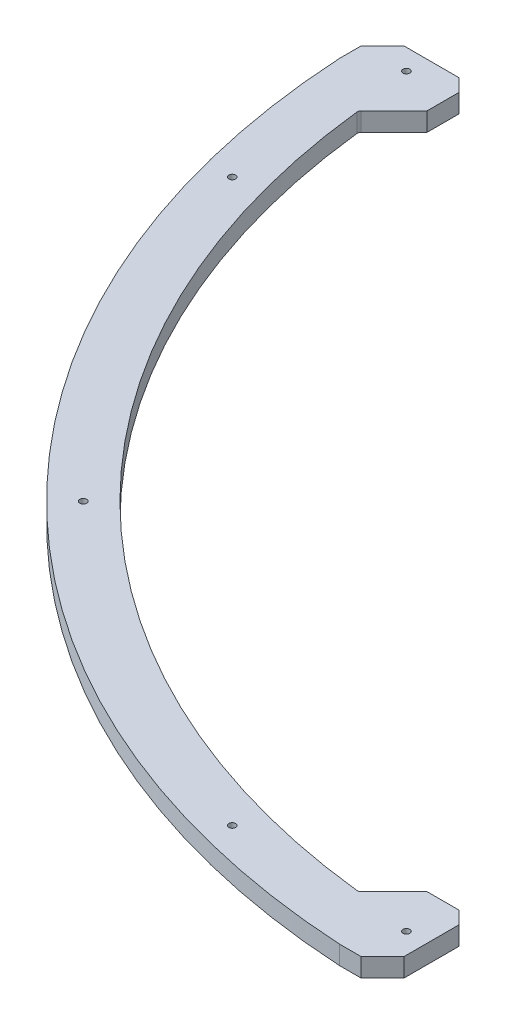
SolidWorks part; units mm, degrees
material "Pine"
ref_plane "Front Plane" through (0, 0, 0) normal (0, 0, 1) x (1, 0, 0)
ref_plane "Top Plane" through (0, 0, 0) normal (0, 1, 0) x (1, 0, 0)
ref_plane "Right Plane" through (0, 0, 0) normal (1, 0, 0) x (0, 0, -1)
ref_plane "Plane1" through (0, 0, 0) normal (0.7071, 0, -0.7071) x (-0.7071, 0, -0.7071)
ref_axis "Axis1" through (0, -0.9128, 0) along (0, 1, 0)
sketch "Sketch1" plane through (0, 0, 0) normal (0, 1, 0) x (1, 0, 0)
  circle A0 centre (0, 0) radius 796.925
  circle A1 centre (0, 0) radius 746.125
  dimension "D1" = 1593.85
  dimension "D2" = 50.8
extrude "Boss-Extrude1" add sketch "Sketch1" along normal blind 18.2562
sketch "Sketch3" plane through (0, 18.2562, 0) normal (0, 1, 0) x (1, 0, 0)
  line L0 (-796.925, 0) -> (0, 0)
  line L1 (0, 0) -> (0, -796.925)
  circle A0 centre (0, 0) radius 796.925 construction
  arc A1 (0, -796.925) -> (-796.925, 0) centre (0, 0) ccw
extrude "Cut-Extrude2" cut sketch "Sketch3" against normal through all
sketch "Sketch4" plane through (0, 18.2562, 0) normal (0, 1, 0) x (1, 0, 0)
  line L1 (-796.925, 44.45) -> (-708.025, 44.45) construction
  line L2 (-796.925, 44.45) -> (-796.925, -44.45) construction
  line L3 (-796.925, -44.45) -> (-708.025, -44.45) construction
  line L4 (-708.025, 44.45) -> (-708.025, -44.45) construction
  line L5 (-752.475, -44.45) -> (-752.475, 44.45) construction
  line L6 (-796.925, 0) -> (-708.025, 0) construction
  line L7 (-44.45, -796.925) -> (44.45, -796.925) construction
  line L8 (-44.45, -796.925) -> (-44.45, -708.025) construction
  line L9 (-44.45, -708.025) -> (44.45, -708.025) construction
  line L10 (44.45, -796.925) -> (44.45, -708.025) construction
  line L11 (0, -708.025) -> (0, -796.925) construction
  line L12 (-44.45, -752.475) -> (44.45, -752.475) construction
  line L13 (-796.925, -44.45) -> (-708.025, -44.45)
  line L14 (-796.925, -44.45) -> (-796.925, 0)
  line L15 (-796.925, 0) -> (-708.025, 0)
  line L16 (-708.025, -44.45) -> (-708.025, 0)
  line L17 (-44.45, -796.925) -> (0, -796.925)
  line L18 (-44.45, -796.925) -> (-44.45, -708.025)
  line L19 (-44.45, -708.025) -> (0, -708.025)
  line L20 (0, -796.925) -> (0, -708.025)
  point P0 (-752.475, 0)
  point P4 (0, -752.475)
  dimension "D1" = 88.9
  dimension "D2" = 88.9
extrude "Boss-Extrude2" add sketch "Sketch4" against normal up to surface (18.2563 mm away) up to face at (-465.6565, 0, 465.6565)
sketch "Sketch10" plane through (0, 18.2562, 0) normal (0, 1, 0) x (1, 0, 0)
  line L1 (-796.925, 0) -> (-708.025, 0)
  line L2 (-796.925, 0) -> (-796.925, -1.5875)
  line L3 (-796.925, -1.5875) -> (-708.025, -1.5875)
  line L4 (-708.025, 0) -> (-708.025, -1.5875)
  line L6 (0, -708.025) -> (-1.5875, -708.025)
  line L7 (0, -708.025) -> (0, -796.925)
  line L8 (0, -796.925) -> (-1.5875, -796.925)
  line L9 (-1.5875, -708.025) -> (-1.5875, -796.925)
  line L10 (-708.025, -44.45) -> (-708.025, 0) construction
  line L11 (-44.45, -796.925) -> (0, -796.925) construction
  line L12 (0, -708.025) -> (0, -796.925) construction
  line L13 (0, -708.025) -> (-44.45, -708.025) construction
  dimension "D1" = 1.5875
extrude "Cut-Extrude3" cut sketch "Sketch10" against normal through all
sketch "Sketch11" plane through (0, 18.2562, 0) normal (0, 1, 0) x (1, 0, 0)
  line L0 (-795.6844, -44.45) -> (-795.6844, -1.5875)
  line L1 (-796.925, -1.5875) -> (-708.025, -1.5875) construction
  line L2 (-795.6844, -1.5875) -> (-796.925, -1.5875)
  line L3 (-796.925, -1.5875) -> (-796.925, -44.45)
  line L4 (-796.925, -44.45) -> (-795.6844, -44.45)
  line L5 (-44.45, -795.6844) -> (-1.5875, -795.6844)
  line L6 (-1.5875, -708.025) -> (-1.5875, -796.925) construction
  line L7 (-1.5875, -795.6844) -> (-1.5875, -796.925)
  line L8 (-1.5875, -796.925) -> (-44.45, -796.925)
  line L9 (-44.45, -796.925) -> (-44.45, -795.6844)
extrude "Cut-Extrude4" cut sketch "Sketch11" against normal through all
sketch "Sketch12" plane through (0, 18.2562, 0) normal (0, 1, 0) x (1, 0, 0)
  line L4 (-45.7311, -708.025) -> (-79.5755, -741.8694)
  line L6 (-708.025, -45.7311) -> (-741.8694, -79.5755)
  line L7 (0, 0) -> (-563.5111, -563.5111) construction
  line L8 (-708.025, -44.45) -> (-708.025, -1.5875) construction
  line L9 (-708.025, -45.7311) -> (-708.025, -44.45)
  line L10 (-708.025, -44.45) -> (-744.7998, -44.45)
  line L13 (-1.5875, -708.025) -> (-44.45, -708.025) construction
  line L14 (-45.7311, -708.025) -> (-44.45, -708.025)
  line L15 (-44.45, -708.025) -> (-44.45, -744.7998)
  arc A0 (-744.7998, -44.45) -> (-44.45, -744.7998) centre (0, 0) ccw construction
  arc A1 (-744.7998, -44.45) -> (-741.8694, -79.5755) centre (0, 0) ccw
  arc A2 (-79.5755, -741.8694) -> (-44.45, -744.7998) centre (0, 0) ccw
  arc A3 (-795.6844, -44.45) -> (-44.45, -795.6844) centre (0, 0) ccw construction
  line M10 (-44.45, -708.025) -> (-44.45, -744.7998)
  arc M11 (-44.45, -744.7998) -> (-744.7998, -44.45) centre (0, 0) cw
  line M12 (-744.7998, -44.45) -> (-708.025, -44.45)
  dimension "D1" = 468.3125
  dimension "D2" = 468.3125
extrude "Boss-Extrude4" add sketch "Sketch12" against normal through all contours L4 M10 M11 | L6 M12 M11 region at (-56.2149, 18.2562, 731.2558) region at (-731.2558, 18.2562, 56.2149)
sketch "Sketch13" plane through (0, 0, 0) normal (0, -1, 0) x (1, 0, 0)
  line L0 (397.0484, 397.0484) -> (-397.0484, -397.0484) construction
  line L1 (-397.0484, -397.0484) -> (-960.5595, 166.4626) construction
  line L2 (-960.5595, 166.4626) -> (-166.4626, 960.5595) construction
  line L3 (-166.4626, 960.5595) -> (397.0484, 397.0484) construction
  line L4 (-751.8547, -42.2422) -> (42.2422, 751.8547) construction
  line L5 (-949.6621, 177.3601) -> (-740.9573, -31.3448) construction
  line L6 (-177.3601, 949.6621) -> (31.3448, 740.9573) construction
  line L7 (-747.6063, -24.6957) -> (24.6957, 747.6063) construction
  line L8 (-845.3097, 73.0076) -> (-73.0076, 845.3097) construction
  line L9 (-459.1587, 459.1587) -> (0, 0) construction
  line L10 (-795.6844, 1.5875) -> (-708.025, 1.5875) construction
  line L11 (-708.025, 45.7311) -> (-708.025, 1.5875) construction
  arc A0 (-44.45, 795.6844) -> (-795.6844, 44.45) centre (0, 0) ccw construction
  point P3 (0, 0)
  point P11 (-563.5111, 563.5111)
  point P25 (-773.8895, 1.5875)
  point P26 (-721.3231, 1.5875)
  point P27 (0, 0)
  point P31 (-708.025, 14.8856)
  dimension "D1" = 295.1532
  dimension "D2" = 1123.0226
  dimension "D3" = 285.75
  dimension "D4" = 1092.2
  dimension "D5" = 37.1701
  dimension "D6" = 55.9764
sketch "Sketch14" plane through (0, 0, 0) normal (0, -1, 0) x (1, 0, 0)
  line L0 (-166.4626, 960.5595) -> (397.0484, 397.0484) construction
  line L1 (-177.3601, 949.6621) -> (31.3448, 740.9573) construction
  line L2 (-960.5595, 166.4626) -> (-166.4626, 960.5595) construction
  line L3 (-751.8547, -42.2422) -> (42.2422, 751.8547) construction
  line L4 (-747.6063, -24.6957) -> (24.6957, 747.6063) construction
  line L5 (-397.0484, -397.0484) -> (-960.5595, 166.4626) construction
  line L6 (-949.6621, 177.3601) -> (-740.9573, -31.3448) construction
  line L7 (-166.4626, 960.5595) -> (42.2422, 751.8547)
  line L8 (-177.3601, 949.6621) -> (24.6957, 747.6063)
  line L9 (-960.5595, 166.4626) -> (-949.6621, 177.3601)
  line L10 (-751.8547, -42.2422) -> (42.2422, 751.8547)
  line L11 (-747.6063, -24.6957) -> (24.6957, 747.6063)
  line L12 (-751.8547, -42.2422) -> (-960.5595, 166.4626)
  line L13 (-949.6621, 177.3601) -> (-747.6063, -24.6957)
  line L14 (-177.3601, 949.6621) -> (-166.4626, 960.5595)
extrude "Cut-Extrude5" cut sketch "Sketch14" against normal through all
ref_plane "Plane2" through (-563.5111, 0, 563.5111) normal (-0.7071, 0, 0.7071) x (0.7071, 0, 0.7071)
sketch "Sketch16" plane through (0, 18.2562, 0) normal (0, 1, 0) x (1, 0, 0)
  line L4 (-773.8895, -1.5875) -> (-795.6844, -23.3824) construction
  line L5 (-708.025, -14.8856) -> (-721.3231, -1.5875) construction
  line L6 (-1.5875, -721.3231) -> (-14.8856, -708.025) construction
  line L7 (-23.3824, -795.6844) -> (-1.5875, -773.8895) construction
  point P0 (-752.0965, -22.4506)
  point P5 (-22.4506, -752.0965)
  dimension "D1" = 30.1625
  dimension "D2" = 36.5125
  dimension "D3" = 36.5125
  dimension "D4" = 30.1625
hole_wizard "1/4 Clearance Hole3" positions "Sketch17" profile "Sketch18" hole size "1/4" standard "ANSI Inch" end condition up to next
sketch "Sketch17" plane through (0, 18.2562, 0) normal (0, 1, 0) x (1, 0, 0)
  point P0 (-752.0965, -22.4506)
  point P4 (-22.4506, -752.0965)
sketch "Sketch18" plane through (-752.0965, 18.2562, 22.4506) normal (1, 0, 0) x (0, 0, 1)
  line L0 (0, 0) -> (0, 18.2562)
  line L1 (0, 18.2562) -> (3.3782, 18.2562)
  line L2 (3.3782, 18.2562) -> (3.3782, 0)
  line L5 (3.3782, 0) -> (0, 0)
  line L11 (0, -6.35) -> (0, 107.95) construction
  dimension "Thru Hole Dia." = 6.7564
  dimension "Thru Hole Depth" = 18.2562
sketch "Sketch5" plane through (0, 18.2562, 0) normal (0, 1, 0) x (1, 0, 0)
  line L8 (-197.5656, -747.6063) -> (-747.6063, -197.5656) construction
  line L9 (-545.5506, -545.5506) -> (-6.6134, -6.6134) construction
  line L10 (-773.8895, -1.5875) -> (-795.6844, -23.3824) construction
  line L13 (-708.025, -14.8856) -> (-721.3231, -1.5875) construction
  point P4 (-472.586, -472.586)
  point P23 (-545.5506, -545.5506)
  point P26 (-747.6063, -197.5656)
  point P27 (-197.5656, -747.6063)
  dimension "D1" = 546.1
  dimension "D2" = 260.35
  dimension "D3" = 157.1625
  dimension "D4" = 157.1625
hole_wizard "1/4 Clearance Hole1" positions "Sketch8" profile "Sketch9" hole size "1/4" standard "ANSI Inch" end condition up to next
sketch "Sketch8" plane through (0, 18.2562, 0) normal (0, 1, 0) x (1, 0, 0)
  point P3 (-747.6063, -197.5656)
  point P7 (-545.5506, -545.5506)
  point P10 (-197.5656, -747.6063)
sketch "Sketch9" plane through (-747.6063, 18.2562, 197.5656) normal (1, 0, 0) x (0, 0, 1)
  line L0 (0, 0) -> (0, 18.2562)
  line L1 (0, 18.2562) -> (3.3782, 18.2562)
  line L2 (3.3782, 18.2562) -> (3.3782, 0)
  line L5 (3.3782, 0) -> (0, 0)
  line L11 (0, -6.35) -> (0, 107.95) construction
  dimension "Thru Hole Dia." = 6.7564
  dimension "Thru Hole Depth" = 18.2562
sketch "Sketch19" plane through (0, 18.2562, 0) normal (0, 1, 0) x (1, 0, 0)
  line L0 (-774.5471, -2.2451) -> (-720.6656, -2.2451)
  line L1 (-708.025, -14.8856) -> (-721.3231, -1.5875) construction
  line L2 (-720.6656, -2.2451) -> (-747.6063, 24.6957)
  line L3 (-747.6063, 24.6957) -> (-774.5471, -2.2451)
  line L4 (-773.8895, -1.5875) -> (-795.6844, -23.3824) construction
  line L6 (-708.3177, -14.5929) -> (-708.025, -14.8856)
  line L7 (-708.025, -14.8856) -> (-708.025, -45.7311)
  line L8 (0, 0) -> (-563.5111, -563.5111) construction
  line L9 (-14.8856, -708.025) -> (-45.7311, -708.025)
  line L10 (-14.5929, -708.3177) -> (-14.8856, -708.025)
  line L12 (24.6957, -747.6063) -> (-2.2451, -774.5471)
  line L13 (-2.2451, -720.6656) -> (24.6957, -747.6063)
  line L14 (-2.2451, -774.5471) -> (-2.2451, -720.6656)
  line L15 (-708.3177, -14.5929) -> (-708.3177, -46.0238)
  line L16 (-708.025, -45.7311) -> (-741.8694, -79.5755) construction
  line L17 (-708.3177, -46.0238) -> (-708.025, -45.7311)
  line L18 (-46.0238, -708.3177) -> (-45.7311, -708.025)
  line L19 (-14.5929, -708.3177) -> (-46.0238, -708.3177)
  arc A0 (-795.6844, -44.45) -> (-44.45, -795.6844) centre (0, 0) ccw construction
  point P27 (0, 0)
  dimension "D1" = 38.1
  dimension "D2" = 55.5625
  dimension "D3" = 38.1
  dimension "D4" = 22.225
extrude "Cut-Extrude6" cut sketch "Sketch19" against normal through all
sketch "Sketch20" plane through (0, 18.2562, 0) normal (0, 1, 0) x (1, 0, 0)
  line L0 (-795.6844, -23.3824) -> (-796.5558, -24.2538)
  line L1 (-774.5471, -2.2451) -> (-795.6844, -23.3824) construction
  line L2 (-795.6844, -44.45) -> (-795.6844, -23.3824) construction
  line L3 (-795.6844, -44.45) -> (-795.6844, -23.3824)
  line L4 (-23.3824, -795.6844) -> (-24.2538, -796.5558)
  line L5 (-23.3824, -795.6844) -> (-2.2451, -774.5471) construction
  line L6 (-23.3824, -795.6844) -> (-44.45, -795.6844) construction
  line L7 (-23.3824, -795.6844) -> (-44.45, -795.6844)
  line L8 (-708.3177, -14.5929) -> (-720.6656, -2.2451) construction
  line L9 (-708.3177, -14.5929) -> (-720.6656, -2.2451)
  line L10 (-774.5471, -2.2451) -> (-795.6844, -23.3824)
  line L11 (-708.3177, -46.0238) -> (-742.1055, -77.3429)
  line L12 (-708.3177, -46.0238) -> (-741.8694, -79.5755) construction
  line L13 (-708.3177, -46.0238) -> (-741.8694, -79.5755)
  arc A0 (-795.6844, -44.45) -> (-796.5558, -24.2538) centre (0, 0) cw
  arc A1 (-44.45, -795.6844) -> (-24.2538, -796.5558) centre (0, 0) ccw
  arc A4 (-742.1055, -77.3429) -> (-741.8694, -79.5755) centre (0, 0) ccw
  dimension "D1" = 69.2251
  dimension "D2" = 67.9927
  dimension "D3" = 90
  dimension "D4" = 22.225
  dimension "D5" = 68.2625
  dimension "D6" = 76.0418
fillet "Fillet4" radius 3.3782 2 edges at (-741.8694, 9.1281, 79.5755) (-79.5755, 9.1281, 741.8694)
